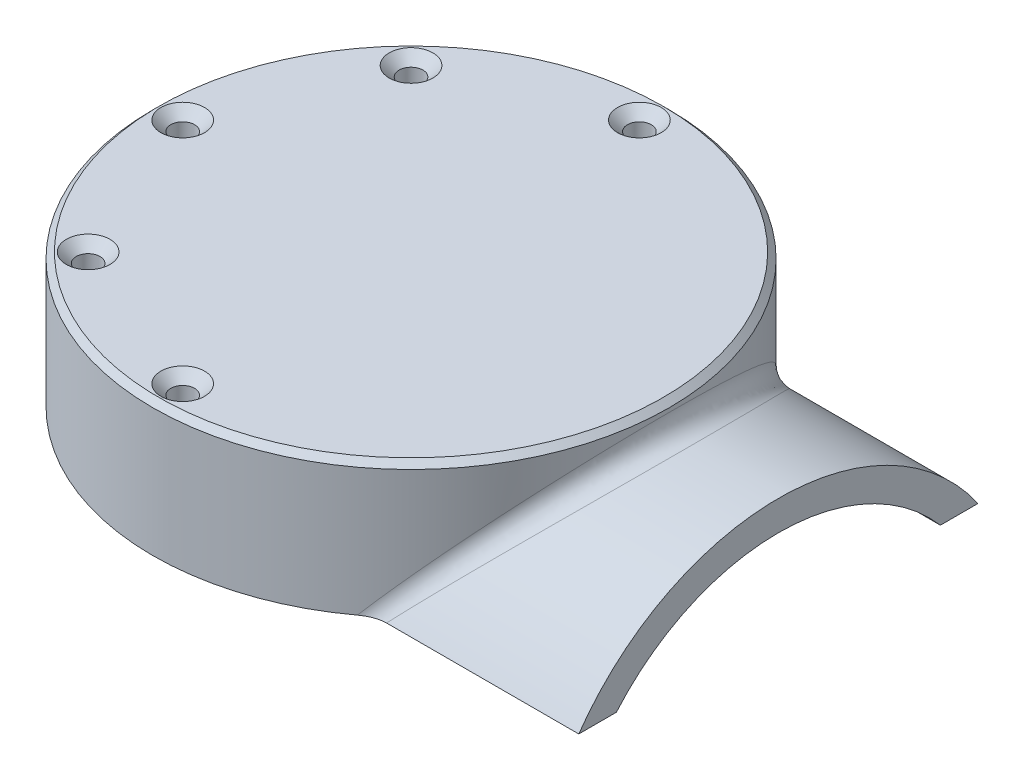
SolidWorks part; units mm, degrees
material "ПК/АБС"
ref_plane "Спереди" through (0, 0, 0) normal (0, 0, 1) x (1, 0, 0)
ref_plane "Сверху" through (0, 0, 0) normal (0, 1, 0) x (1, 0, 0)
ref_plane "Справа" through (0, 0, 0) normal (1, 0, 0) x (0, 0, -1)
sketch "Эскиз1" plane through (0, 0, 0) normal (0, 0, 1) x (1, 0, 0)
  line L0 (0, 0) -> (0, 41295.6463) construction
  line L1 (0, 0) -> (-26, 0)
  line L2 (-26, 0) -> (-26, 27.5)
  line L3 (-26, 27.5) -> (0, 27.5)
  line L4 (0, 27.5) -> (0, 0)
  line L5 (0, 0) -> (-50000, 0) construction
  dimension "D1" = 52
  dimension "D2" = 27.5
revolve "Повернуть1" add sketch "Эскиз1" angle 360 about L0
sketch "Эскиз2" plane through (0, 0, 0) normal (0, 0, 1) x (1, 0, 0)
  line L0 (0, 0) -> (50000, 0) construction
  line L1 (-26, 0) -> (26, 0) construction
  line L2 (0, 0) -> (0, 24.5)
  line L3 (0, 24.5) -> (37, 24.5)
  line L4 (37, 24.5) -> (37, 0)
  line L5 (37, 0) -> (0, 0)
  point P4 (0, 0)
  dimension "D1" = 49
  dimension "D2" = 37
revolve "Повернуть2" add sketch "Эскиз2" angle 360 about L0
chamfer "Фаска1" distance 0.6 angle 45 1 edges at (0, 27.5, -26)
sketch "Эскиз4" plane through (0, 0, 0) normal (0, 0, 1) x (1, 0, 0)
  line L0 (0, 0) -> (0, 50000) construction
  line L1 (0, 0) -> (-25, 0)
  line L2 (-25, 0) -> (-25, 20)
  line L4 (0, 24.5) -> (0, 0)
  line L6 (0, 24.5) -> (-21, 24.5)
  line L7 (-21, 24.5) -> (-21, 20)
  line L8 (-21, 20) -> (-25, 20)
  line L10 (37, 24.5) -> (25.9999, 24.5) construction
  dimension "D1" = 50
  dimension "D2" = 42
  dimension "D3" = 20
revolve "Вырез-Повернуть1" cut sketch "Эскиз4" angle 360 about L0
sketch "Эскиз5" plane through (0, 0, 0) normal (0, 0, 1) x (1, 0, 0)
  line L0 (0, 0) -> (50000, 0) construction
  line L1 (37, 21.5) -> (37, 0)
  line L2 (0, 0) -> (0, 21.5)
  line L3 (0, 21.5) -> (37, 21.5)
  line L4 (37, -24.5) -> (37, 24.5) construction
  line L8 (0, 0) -> (37, 0)
  dimension "D1" = 43
revolve "Вырез-Повернуть2" cut sketch "Эскиз5" angle 360 about L0
sketch "Эскиз6" plane through (0, 0, 0) normal (0, 1, 0) x (1, 0, 0)
  line L3 (8.7034, -24.5) -> (37, -24.5) construction
  line L4 (8.7034, 24.5) -> (37, 24.5)
  line L5 (37, 24.5) -> (37, -24.5)
  line L6 (37, -24.5) -> (8.7034, -24.5)
  circle A0 centre (0, 0) radius 26 construction
  arc A1 (8.7034, -24.5) -> (8.7034, 24.5) centre (0, 0) ccw construction
  arc A2 (8.7034, -24.5) -> (8.7034, 24.5) centre (0, 0) cw
extrude "Вырез-Вытянуть1" cut sketch "Эскиз6" against normal through all and the other way blind 14
hole_wizard "Зенковка для винта с потайной головкой M21" positions "Эскиз7" profile "Эскиз8" countersink size "M2" standard "HASCO Metric" end condition through all
sketch "Эскиз7" plane through (0, 27.5, 0) normal (0, 1, 0) x (1, 0, 0)
  line L0 (0, 0) -> (-25.4, 0) construction
  circle A0 centre (0, 0) radius 25.4 construction
  circle A1 centre (0, 0) radius 23 construction
  point P0 (-23, 0)
  dimension "D1" = 46
sketch "Эскиз8" plane through (-23, 27.5, 0) normal (1, 0, 0) x (0, 0, 1)
  line L0 (0, 0) -> (0, 15.8461)
  line L1 (0, 15.8461) -> (1.2, 15.8461)
  line L2 (1.2, 15.8461) -> (1.2, 1)
  line L3 (1.2, 1) -> (2.2, 0)
  line L5 (2.2, 0) -> (0, 0)
  line L6 (-1.2, 1) -> (-2.2, 0) construction
  line L11 (0, -6.35) -> (0, 107.95) construction
  dimension "Диаметр сквозного отверстия" = 2.4
  dimension "Глубина сквозного отверстия" = 15.8461
  dimension "Диаметр передней зенковки" = 4.4
  dimension "Угол передней зенковки" = 90
pattern_circular "Круговой массив1" count 3 every 45 about axis through (0, 27.5, 0) along (0, 1, 0) of "Зенковка для винта с потайной головкой M21" other way count 3
fillet "Скругление1" radius 2 1 edges at (0, 24.5, -21)
fillet "Скругление2" radius 2 1 edges at (25.9924, 24.492, 0.6278)
